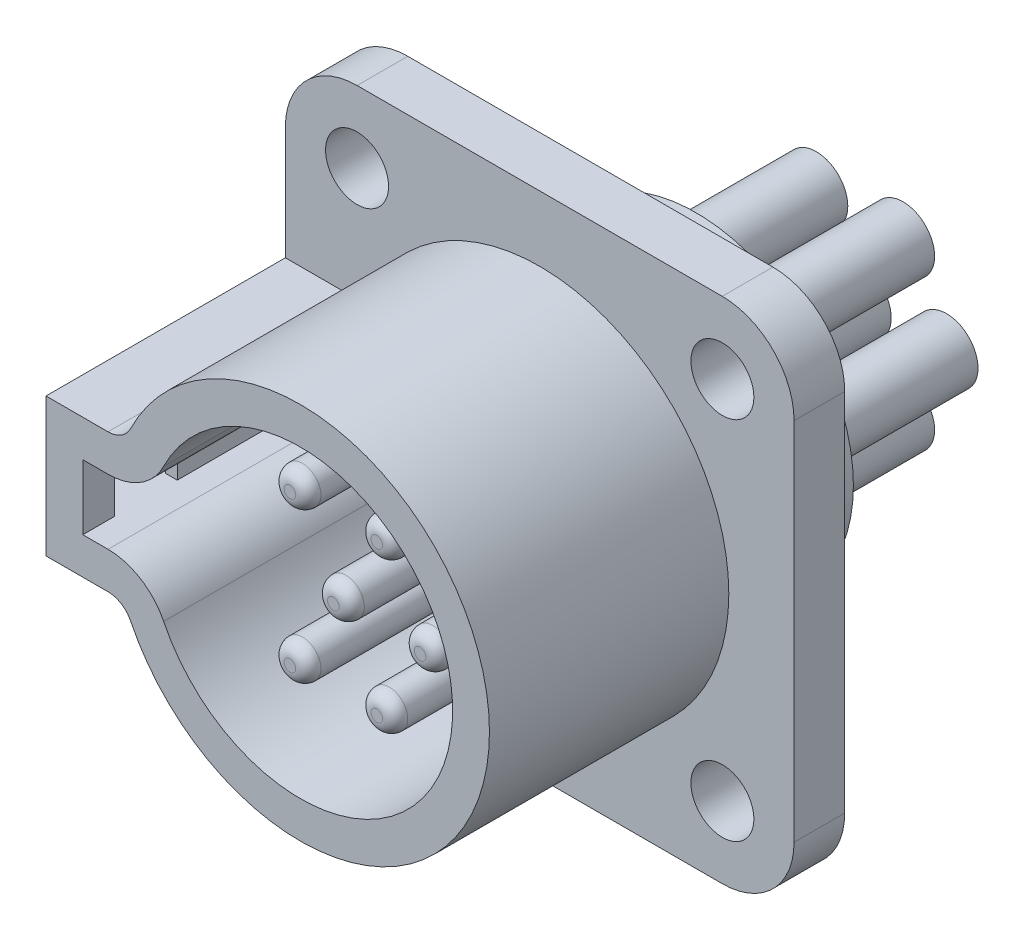
SolidWorks part; units mm, degrees
ref_plane "Front Plane" through (0, 0, 0) normal (0, 0, 1) x (1, 0, 0)
ref_plane "Top Plane" through (0, 0, 0) normal (0, 1, 0) x (1, 0, 0)
ref_plane "Right Plane" through (0, 0, 0) normal (1, 0, 0) x (0, 0, -1)
sketch "Sketch1" plane through (0, 0, 0) normal (0, 0, 1) x (1, 0, 0)
  line L1 (-10.095, 10.095) -> (10.095, 10.095)
  line L2 (-10.095, 10.095) -> (-10.095, -10.095)
  line L3 (-10.095, -10.095) -> (10.095, -10.095)
  line L4 (10.095, 10.095) -> (10.095, -10.095)
  line L5 (-10.095, 10.095) -> (10.095, -10.095) construction
  line L6 (-10.095, -10.095) -> (10.095, 10.095) construction
  point P0 (0, 0)
  dimension "D1" = 20.19
  dimension "D2" = 20.19
extrude "Boss-Extrude1" add sketch "Sketch1" along normal blind 2.01
sketch "Sketch2" plane through (0, 0, 2.01) normal (0, 0, 1) x (1, 0, 0)
  line L0 (0, 0) -> (0, 10.095) construction
  line L1 (10.095, 10.095) -> (-10.095, 10.095) construction
  line L2 (0, 0) -> (-10.095, 0) construction
  line L3 (-10.095, 10.095) -> (-10.095, -10.095) construction
  circle A0 centre (-7.25, 7.25) radius 1.25
  circle A1 centre (7.25, 7.25) radius 1.25
  circle A2 centre (7.25, -7.25) radius 1.25
  circle A3 centre (-7.25, -7.25) radius 1.25
  point P2 (0, 0)
  dimension "D1" = 2.5
  dimension "D2" = 7.25
  dimension "D3" = 7.25
extrude "Cut-Extrude1" cut sketch "Sketch2" against normal up to surface (2.01 mm away) up to face at (0, 0, 0)
fillet "Fillet1" radius 2.85 4 edges at (10.095, -10.095, 1.005) (-10.095, -10.095, 1.005) (10.095, 10.095, 1.005) (-10.095, 10.095, 1.005)
sketch "Sketch4" plane through (0, 0, 2.01) normal (0, 0, 1) x (1, 0, 0)
  line L0 (-10.095, -2.7495) -> (-10.095, 2.7495)
  line L1 (-10.095, 7.245) -> (-10.095, -7.245) construction
  line L2 (-10.095, 2.7495) -> (-7.6339, 2.7495)
  line L3 (-10.095, 0) -> (11.2357, 0) construction
  line L4 (-10.095, -2.7495) -> (-7.6339, -2.7495)
  line L5 (-8.635, -1.2895) -> (-8.635, 1.2895)
  line L6 (-8.635, 1.2895) -> (-7.6339, 1.2895)
  line L7 (-8.635, -1.2895) -> (-7.6339, -1.2895)
  line L8 (0, 10.095) -> (0, -11.6505) construction
  line L9 (7.245, 10.095) -> (-7.245, 10.095) construction
  line L10 (0, 6.045) -> (3.3385, 6.045) construction
  line L11 (0, -6.045) -> (3.3385, -6.045) construction
  line L12 (0, -7.505) -> (3.9298, -7.505) construction
  line L13 (0, 7.505) -> (4.2254, 7.505) construction
  arc A0 (-6.7363, 3.3086) -> (-6.7363, -3.3086) centre (0, 0) cw
  arc A1 (-6.7363, 3.3086) -> (-7.6339, 2.7495) centre (-7.6339, 3.7495) cw
  arc A2 (-6.7363, -3.3086) -> (-7.6339, -2.7495) centre (-7.6339, -3.7495) ccw
  arc A3 (-5.4259, 2.665) -> (-7.6339, 1.2895) centre (-7.6339, 3.7495) cw
  arc A4 (-5.4259, 2.665) -> (-5.4259, -2.665) centre (0, 0) cw
  arc A5 (-5.4259, -2.665) -> (-7.6339, -1.2895) centre (-7.6339, -3.7495) ccw
  dimension "D1" = 1
  dimension "D3" = 15.01
  dimension "D4" = 12.09
extrude "Boss-Extrude2" add sketch "Sketch4" along normal blind 9.5
sketch "Sketch5" plane through (-10.095, 0, 0) normal (-1, 0, 0) x (0, 0, 1)
  line L0 (0, 7.245) -> (0, -7.245) construction
  line L1 (0, 1.2895) -> (10.26, 1.2895)
  line L2 (0, 1.2895) -> (0, -1.2895)
  line L3 (0, -1.2895) -> (10.26, -1.2895)
  line L4 (10.26, 1.2895) -> (10.26, -1.2895)
  line L6 (0, 0) -> (-1.0293, 0) construction
  line L7 (11.51, 2.7495) -> (11.51, -2.7495) construction
  line L8 (11.51, 2.7495) -> (2.01, 2.7495) construction
  line L9 (11.51, -2.7495) -> (2.01, -2.7495) construction
  dimension "D1" = 1.25
  dimension "D2" = 1.46
  dimension "D3" = 1.46
extrude "Cut-Extrude2" cut sketch "Sketch5" against normal blind 1
sketch "Sketch6" plane through (-9.095, 0, 0) normal (-1, 0, 0) x (0, 0, 1)
  line L0 (0, -1.2895) -> (10.26, -1.2895) construction
  line L1 (10.26, 1.2895) -> (7.76, 1.2895)
  line L2 (10.26, 1.2895) -> (10.26, -1.2895)
  line L3 (10.26, -1.2895) -> (7.76, -1.2895)
  line L4 (7.76, 1.2895) -> (7.76, -1.2895)
  dimension "D1" = 2.5
extrude "Cut-Extrude3" cut sketch "Sketch6" against normal up to next
sketch "Sketch7" plane through (0, 0, 0) normal (0, 0, -1) x (-1, 0, 0)
  circle A0 centre (0, 0) radius 6.25
  dimension "D1" = 12.5
extrude "Boss-Extrude3" add sketch "Sketch7" along normal blind 4.19
sketch "Sketch8" plane through (0, 0, 2.01) normal (0, 0, 1) x (1, 0, 0)
  line L0 (-3.445, 0) -> (5.0962, 0) construction
  circle A0 centre (0, 0) radius 0.73
  circle A2 centre (3.445, 0) radius 0.73
  circle A3 centre (1.7225, 2.9835) radius 0.73
  circle A4 centre (-1.7225, 2.9835) radius 0.73
  circle A5 centre (1.7225, -2.9835) radius 0.73
  circle A6 centre (-1.7225, -2.9835) radius 0.73
  dimension "D1" = 1.46
extrude "Boss-Extrude4" add sketch "Sketch8" along normal blind 8.19 and the other way blind 7
fillet "Fillet2" radius 0.5 6 edges at (-2.4525, -2.9835, 10.2) (2.4525, 2.9835, 10.2) (0.9925, -2.9835, 10.2) (4.175, 0, 10.2) (0.73, 0, 10.2) (-0.9925, 2.9835, 10.2)
sketch "Sketch9" plane through (0, 0, -4.19) normal (0, 0, -1) x (-1, 0, 0)
  circle A0 centre (-1.7225, 2.9835) radius 1
  circle A1 centre (1.7225, 2.9835) radius 1
  circle A2 centre (0, 0) radius 1
  circle A3 centre (-3.445, 0) radius 1
  circle A4 centre (-1.7225, -2.9835) radius 1
  circle A5 centre (-1.7225, -2.9835) radius 1
  circle A6 centre (1.7225, -2.9835) radius 1
  point P0 (-1.7225, 2.9835)
  point P1 (1.7225, 2.9835)
  point P3 (-3.445, 0)
  point P5 (0, 0)
  point P7 (-1.7225, -2.9835)
  point P9 (1.7225, -2.9835)
  dimension "D1" = 2
  dimension "D2" = 2
  dimension "D3" = 2
  dimension "D4" = 2
  dimension "D5" = 2
  dimension "D6" = 2
extrude "Extrude-Thin1" add sketch "Sketch9" along normal blind 6.5 thin contours A0 | A1 | A2 | A3 | A4 | A6 thin type one direction wall 0.25
equation "\"D2@Sketch1\"=\"D1@Sketch1\""
equation "\"D3@Sketch5\"=\"D2@Sketch5\""
equation "\"D2@Sketch9\"=\"D1@Sketch9\""
equation "\"D3@Sketch9\"=\"D1@Sketch9\""
equation "\"D4@Sketch9\"=\"D1@Sketch9\""
equation "\"D5@Sketch9\"=\"D1@Sketch9\""
equation "\"D6@Sketch9\"=\"D1@Sketch9\""
